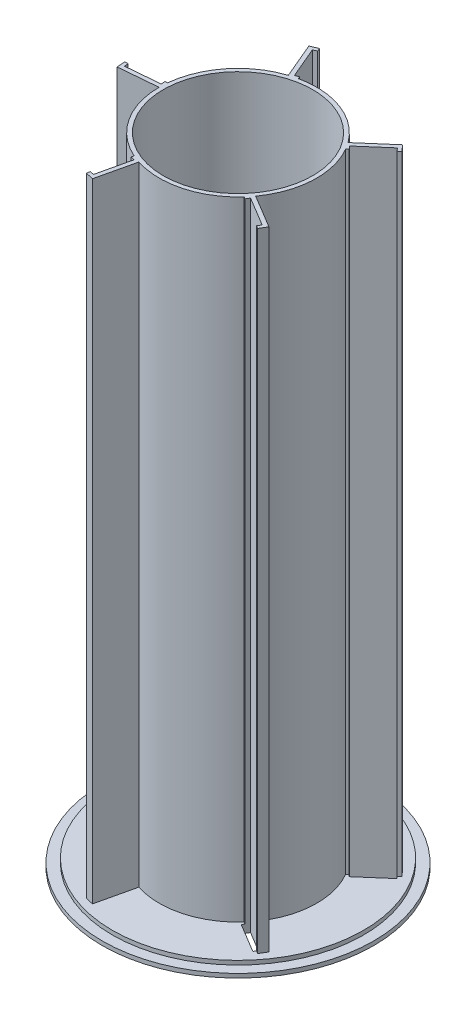
SolidWorks part; units mm, degrees
ref_plane "Front Plane" through (0, 0, 0) normal (0, 0, 1) x (1, 0, 0)
ref_plane "Top Plane" through (0, 0, 0) normal (0, 1, 0) x (1, 0, 0)
ref_plane "Right Plane" through (0, 0, 0) normal (1, 0, 0) x (0, 0, -1)
sketch "Sketch1" plane through (0, 0, 0) normal (0, 1, 0) x (1, 0, 0)
  circle A0 centre (0, 0) radius 40
  dimension "D1" = 80
extrude "Boss-Extrude1" add sketch "Sketch1" along normal blind 2.4
sketch "Sketch2" plane through (0, 2.4, 0) normal (0, 1, 0) x (1, 0, 0)
  line L10 (0, 0) -> (-22, 0) construction
  line L16 (-22, 6.8998) -> (-22, -13.9369) construction
  circle A2 centre (0, 0) radius 22
  circle A3 centre (0, 0) radius 23.2
  point P4 (-22, 0)
  point P7 (-22, 0)
  point P8 (-22, 0)
  point P10 (0, 0)
  point P11 (-19.9686, 3.8219)
  dimension "D1" = 44
  dimension "D2" = 1.2
extrude "Boss-Extrude2" add sketch "Sketch2" along normal blind 185
sketch "Sketch5" plane through (0, 2.4, 0) normal (0, 1, 0) x (1, 0, 0)
  circle A0 centre (0, 0) radius 40 construction
  circle A1 centre (0, 0) radius 40
  circle A2 centre (0, 0) radius 37
  dimension "D1" = 3
sketch "Sketch6" plane through (0, 2.4, 0) normal (0, 1, 0) x (1, 0, 0)
  line L0 (0, 0) -> (-23.2, 0) construction
  line L1 (-23.2, 0) -> (-22, 0)
  line L2 (-22.6, 0) -> (-34.5543, -1.0459)
  line L3 (-22.6, 0) -> (-22.8092, 2.3909)
  line L4 (-34.5543, -1.0459) -> (-34.7635, 1.345)
  line L5 (-22.8092, 2.3909) -> (-34.7635, 1.345)
  line L6 (-22.6, 0) -> (-22.6, -9.7949) construction
  line L7 (-28.7863, 1.8679) -> (-30.8504, 25.4608) construction
  circle A4 centre (0, 0) radius 23.2 construction
  circle A5 centre (0, 0) radius 23.2 construction
  circle A6 centre (0, 0) radius 22 construction
  circle A7 centre (0, 0) radius 22 construction
  circle A8 centre (0, 0) radius 40 construction
  point P11 (-40, 0)
  point P17 (-28.7863, 1.8679)
  point P22 (-30.8732, 25.4332)
  dimension "D1" = 85
  dimension "D2" = 12
  dimension "D3" = 2.4
extrude "Boss-Extrude3" add sketch "Sketch6" along normal up to surface (185 mm away) contours L3 L5 L4 L2 region at (-28.6818, 2.4, -0.6725) up to face at (0, 187.4, 23.2)
sketch "Sketch7" plane through (-0.3808, 0, -4.3531) normal (-0.0872, 0, -0.9962) x (-0.9962, 0, 0.0872)
  line L0 (33.514, 2.4) -> (23.514, 2.4)
  line L1 (33.514, 2.4) -> (33.514, 187.4)
  line L2 (23.514, 2.4) -> (23.514, 187.4)
  line L3 (33.514, 187.4) -> (23.514, 187.4)
  line L4 (22.7848, 2.4) -> (34.514, 2.4) construction
  line L6 (22.7848, 187.4) -> (34.514, 187.4) construction
  point P9 (23.4399, 191)
  dimension "D1" = 10
  dimension "D2" = 1
extrude "Cut-Extrude4" cut sketch "Sketch7" against normal blind 1.2
pattern_circular "CirPattern1" count 5 over 360 about axis through (0, 187.4, 0) along (0, -1, 0) of "Boss-Extrude3", "Cut-Extrude4"
sketch "Sketch8" plane through (0, 2.4, 0) normal (0, 1, 0) x (1, 0, 0)
  line L0 (-23.7008, 1.1083) -> (-33.6627, 0.2367)
  line L1 (-23.7008, 1.1083) -> (-23.8751, 3.1007)
  line L2 (-33.6627, 0.2367) -> (-33.837, 2.2291)
  line L3 (-23.8751, 3.1007) -> (-33.837, 2.2291)
  line L4 (-6.2699, 22.8833) -> (-10.1772, 32.0883)
  line L5 (-6.2699, 22.8833) -> (-4.4289, 23.6647)
  line L6 (-10.1772, 32.0883) -> (-8.3362, 32.8698)
  line L7 (-4.4289, 23.6647) -> (-8.3362, 32.8698)
  line L8 (27.3729, 19.5949) -> (19.8258, 13.0344)
  line L9 (27.3729, 19.5949) -> (28.685, 18.0855)
  line L10 (19.8258, 13.0344) -> (21.1379, 11.5249)
  line L11 (28.685, 18.0855) -> (21.1379, 11.5249)
  line L12 (27.0946, -19.978) -> (18.5229, -14.8276)
  line L13 (27.0946, -19.978) -> (26.0645, -21.6923)
  line L14 (18.5229, -14.8276) -> (17.4928, -16.5419)
  line L15 (26.0645, -21.6923) -> (17.4928, -16.5419)
  line L16 (-10.6275, -31.942) -> (-8.378, -22.1983)
  line L17 (-10.6275, -31.942) -> (-12.5762, -31.4921)
  line L18 (-8.378, -22.1983) -> (-10.3267, -21.7484)
  line L19 (-12.5762, -31.4921) -> (-10.3267, -21.7484)
  dimension "D1" = 2
  dimension "D2" = 2
  dimension "D3" = 2
  dimension "D4" = 2
  dimension "D5" = 2
extrude "Cut-Extrude5" cut sketch "Sketch8" against normal up to surface (2.4 mm away) up to face at (0, 0, 40)
extrude "Cut-Extrude6" cut sketch "Sketch5" against normal blind 1.2
ref_plane "Plane1" through (0, 58.3546, 0) normal (0, 1, 0) x (1, 0, 0)
